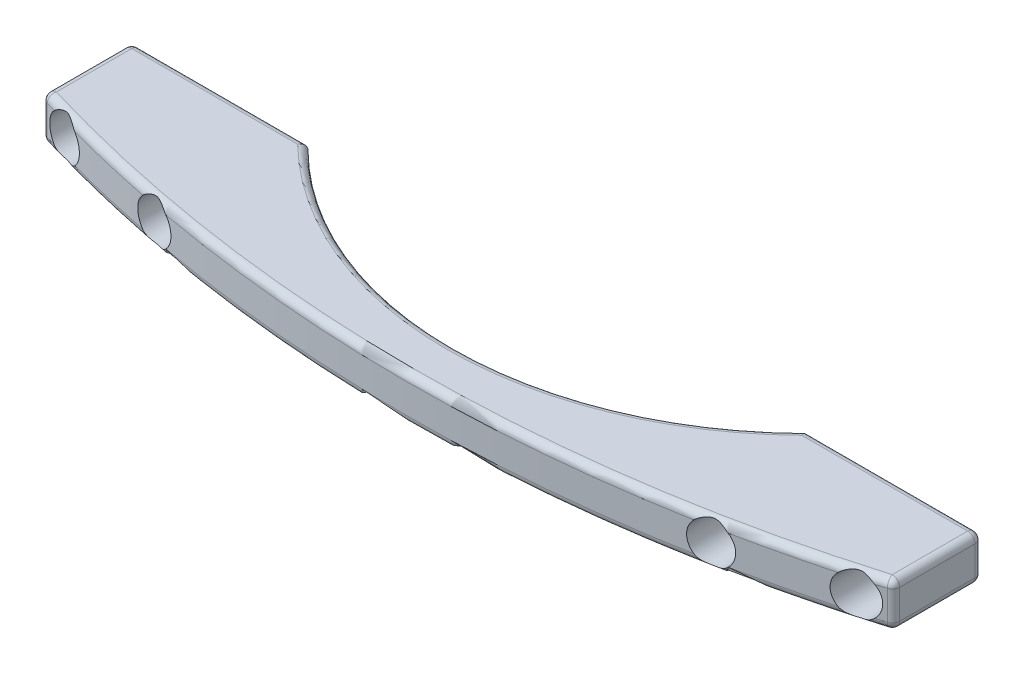
SolidWorks part; units mm, degrees
ref_plane "Front Plane" through (0, 0, 0) normal (0, 0, 1) x (1, 0, 0)
ref_plane "Top Plane" through (0, 0, 0) normal (0, 1, 0) x (1, 0, 0)
ref_plane "Right Plane" through (0, 0, 0) normal (1, 0, 0) x (0, 0, -1)
sketch "Sketch1" plane through (0, 0, 0) normal (0, 1, 0) x (1, 0, 0)
  line L0 (0, 0) -> (0, -19.05)
  line L1 (183.8325, 0) -> (183.8325, -19.05)
  line L2 (0, 0) -> (38.1, 0)
  line L3 (183.8325, 0) -> (145.7325, 0)
  arc A1 (0, -19.05) -> (183.8325, -19.05) centre (91.9163, 284.854) ccw
  arc A2 (38.1, 0) -> (145.7325, 0) centre (91.9162, 53.9467) ccw
  dimension "D6" = 76.2
  dimension "D7" = 317.5
  dimension "D1" = 183.8325
  dimension "D2" = 38.1
  dimension "D3" = 38.1
  dimension "D4" = 19.05
  dimension "D5" = 19.05
extrude "Boss-Extrude1" add sketch "Sketch1" along normal blind 9.525
ref_plane "Plane1" through (91.9163, 0, 0) normal (1, 0, 0) x (0, 0, -1)
sketch "Sketch2" plane through (0, 0, 0) normal (0, 0, -1) x (-1, 0, 0)
  line L0 (-31.75, 4.7625) -> (-38.1, 4.7625) construction
  line L1 (-38.1, 9.525) -> (-38.1, 0) construction
  line L2 (-6.35, 4.7625) -> (0, 4.7625) construction
  line L3 (0, 9.525) -> (0, 0) construction
  circle A0 centre (-6.35, 4.7625) radius 2.286
  circle A1 centre (-31.75, 4.7625) radius 2.286
  dimension "D1" = 4.572
  dimension "D2" = 25.4
extrude "Cut-Extrude1" cut sketch "Sketch2" against normal through all
ref_plane "Plane2" through (91.9163, 0, 0) normal (-1, 0, 0) x (0, 0, 1)
ref_plane "Plane3" through (0, 0, 27.94) normal (0, 0, -1) x (-1, 0, 0)
sketch "Sketch3" plane through (0, 0, 27.94) normal (0, 0, -1) x (-1, 0, 0)
  circle A0 centre (-31.75, 4.7625) radius 4.445
  circle A1 centre (-6.35, 4.7625) radius 4.445
  dimension "D1" = 8.89
  dimension "D2" = 8.89
extrude "Cut-Extrude2" cut sketch "Sketch3" along normal blind 15.875
mirror "Mirror1" about plane through (91.9163, 0, 0) normal (-1, 0, 0) of "Cut-Extrude2", "Cut-Extrude1"
fillet "Fillet1" radius 1.5875 16 edges at (0, 4.7625, 0) (0, 4.7625, 19.05) (0, 0, 9.525) (91.9163, 0, 32.646) (183.8325, 0, 9.525) (164.7825, 0, 0) (91.9163, 0, 22.2533) (19.05, 0, 0) (91.9163, 9.525, 22.2533) (164.7825, 9.525, 0) (183.8325, 9.525, 9.525) (91.9163, 9.525, 32.646) (0, 9.525, 9.525) (19.05, 9.525, 0) (183.8325, 4.7625, 0) (183.8325, 4.7625, 19.05)
